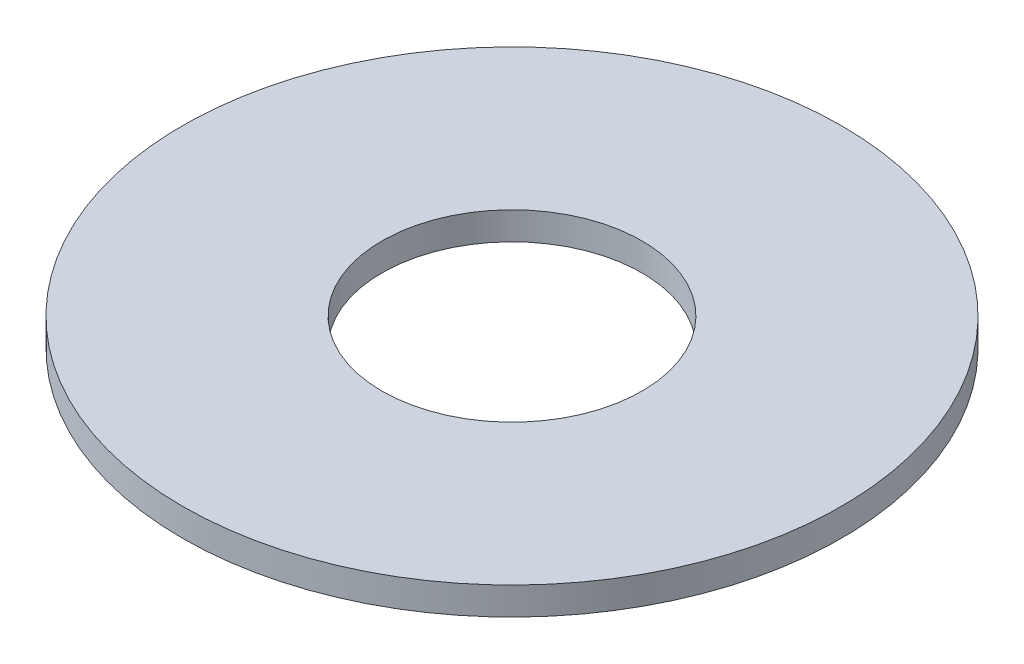
SolidWorks part; units mm, degrees
ref_plane "Front Plane" through (0, 0, 0) normal (0, 0, 1) x (1, 0, 0)
ref_plane "Top Plane" through (0, 0, 0) normal (0, 1, 0) x (1, 0, 0)
ref_plane "Right Plane" through (0, 0, 0) normal (1, 0, 0) x (0, 0, -1)
sketch "Sketch1" plane through (0, 0, 0) normal (0, 1, 0) x (1, 0, 0)
  circle A0 centre (0, 0) radius 95
  dimension "FLANGE_OD" = 190
extrude "Boss-Extrude1" add sketch "Sketch1" along normal blind 8
sketch "Sketch2" plane through (0, 0, 0) normal (0, 1, 0) x (1, 0, 0)
  circle A0 centre (0, 0) radius 37.5
  dimension "BORE_D" = 75
extrude "Cut-Extrude1" cut sketch "Sketch2" along normal through all
sketch "Sketch3" plane through (0, 8, 0) normal (0, 1, 0) x (1, 0, 0)
  circle A0 centre (0, 0) radius 25.4345 construction
  circle A1 centre (-25.4345, 0) radius 5.8944
  dimension "BOLT_D" = 11.7888
  dimension "BOLT_PCD" = 50.869
extrude "Cut-Extrude2" cut sketch "Sketch3" against normal blind 5.5057 rebuild error yes
pattern_circular "CirPattern1" count 4 over 360 rebuild error yes
